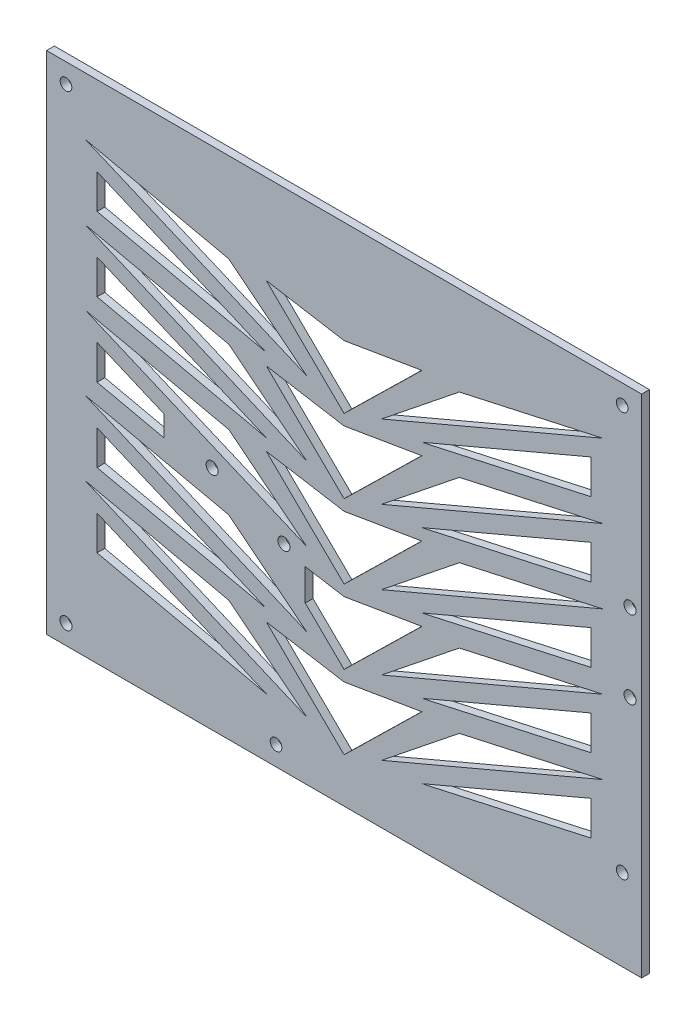
SolidWorks part; units mm, degrees
material "PE 低密度结膜"
ref_plane "前视基准面" through (0, 0, 0) normal (0, 0, 1) x (1, 0, 0)
ref_plane "上视基准面" through (0, 0, 0) normal (0, 1, 0) x (1, 0, 0)
ref_plane "右视基准面" through (0, 0, 0) normal (1, 0, 0) x (0, 0, -1)
sketch "草图1" plane through (0, 0, 0) normal (0, 0, 1) x (1, 0, 0)
  line L1 (-76.5, -55) -> (76.5, -55)
  line L2 (-76.5, -55) -> (-76.5, 55)
  line L3 (-76.5, 55) -> (76.5, 55)
  line L4 (76.5, -55) -> (76.5, 55)
  line L5 (-76.5, -55) -> (76.5, 55) construction
  line L6 (-76.5, 55) -> (76.5, -55) construction
  point P0 (0, 0)
  dimension "D1" = 110
  dimension "D2" = 153
extrude "凸台-拉伸1" add sketch "草图1" along normal blind 2
sketch "草图2" plane through (0, 0, 2) normal (0, 0, 1) x (1, 0, 0)
  circle A0 centre (-33.9424, 3.3504) radius 1.55
  circle A1 centre (-15.4689, -4.3131) radius 1.55
  dimension "D1" = 3.1
  dimension "D2" = 3.1
extrude "切除-拉伸1" cut sketch "草图2" against normal blind 10
sketch "草图3" plane through (0, 0, 2) normal (0, 0, 1) x (1, 0, 0)
  circle A0 centre (73.5, 26) radius 1.55
  circle A1 centre (73.5, 6) radius 1.55
  dimension "D1" = 3.1
extrude "切除-拉伸2" cut sketch "草图3" against normal blind 10
sketch "草图4" plane through (0, 0, 12) normal (0, 0, 1) x (1, 0, 0)
  circle A0 centre (71.5, -34) radius 1.5
extrude "切除-拉伸3" cut sketch "草图4" against normal blind 14
sketch "草图6" plane through (0, 0, 2) normal (0, 0, 1) x (1, 0, 0)
  circle A0 centre (-71.5, -50) radius 1.55
  dimension "D1" = 3.1
extrude "切除-拉伸4" cut sketch "草图6" against normal blind 14
sketch "草图9" plane through (0, 0, 12) normal (0, 0, 1) x (1, 0, 0)
  circle A0 centre (-71.5, 70) radius 1.5
extrude "切除-拉伸6" cut sketch "草图9" against normal blind 14 rebuild error yes
sketch "草图10" plane through (0, 0, 12) normal (0, 0, 1) x (1, 0, 0)
  circle A0 centre (-17.5, -50) radius 1.5
extrude "切除-拉伸7" cut sketch "草图10" against normal blind 21
sketch "Sketch2" plane through (0, 0, 0) normal (0, 0, -1) x (-1, 0, 0)
  line L0 (-76.5, -55) -> (-76.5, 55) construction
  line L1 (-76.5, 55) -> (76.5, 55)
  line L2 (-76.5, 55) -> (-76.5, 75)
  line L3 (-76.5, 75) -> (76.5, 75)
  line L4 (76.5, 55) -> (76.5, 75)
  line L5 (-76.5, 55) -> (76.5, 55) construction
  circle A0 centre (-71.5, 70) radius 1.5
  circle A1 centre (71.5, 70) radius 1.5
  dimension "D1" = 3
  dimension "D2" = 5
  dimension "D3" = 5
  dimension "D4" = 3
  dimension "D5" = 5
  dimension "D7" = 5
  dimension "D6" = 20
extrude "Boss-Extrude1" add sketch "Sketch2" against normal up to surface (2 mm away) up to face at (-19, -50, 2)
sketch "Sketch4" plane through (0, 0, 0) normal (0, 0, -1) x (-1, 0, 0)
  line L0 (0, 75) -> (0, -55) construction
  line L1 (76.5, 75) -> (-76.5, 75) construction
  line L2 (76.5, -55) -> (-76.5, -55) construction
  line L3 (0, 29.6526) -> (20, 33.0228)
  line L7 (9.6268, 17.0228) -> (29.6268, 33.0228)
  line L8 (29.6268, 33.0228) -> (66.5, 41.1778)
  line L9 (66.5, 41.1778) -> (9.6268, 17.0228)
  line L10 (76.5, 75) -> (76.5, -55) construction
  line L11 (20, 17.0228) -> (63.5111, 35.5027)
  line L12 (20, 17.0228) -> (63.5111, 26.6459)
  line L13 (63.5111, 26.6459) -> (63.5111, 35.5027)
  line L14 (-63.5111, 26.6459) -> (-63.5111, 35.5027)
  line L15 (-20, 17.0228) -> (-63.5111, 26.6459)
  line L16 (-20, 17.0228) -> (-63.5111, 35.5027)
  line L17 (-66.5, 41.1778) -> (-9.6268, 17.0228)
  line L18 (-29.6268, 33.0228) -> (-66.5, 41.1778)
  line L19 (-9.6268, 17.0228) -> (-29.6268, 33.0228)
  line L21 (0, 29.6526) -> (-20, 33.0228)
  line L22 (-20, 33.0228) -> (0, 13.4456)
  line L23 (0, 13.4456) -> (20, 33.0228)
  dimension "D1" = 20
  dimension "D5" = 10
extrude "Cut-Extrude2" cut sketch "Sketch4" against normal blind 10
pattern_linear "LPattern2" count 2 spacing 19 along (0, 1, 0) of "Cut-Extrude2"
pattern_linear "LPattern3" count 4 spacing 19 along (0, -1, 0) of "Cut-Extrude2"
sketch "Sketch5" plane through (0, 0, 0) normal (0, 0, -1) x (-1, 0, 0)
  line L0 (46.3639, 9.22) -> (46.3639, 3.8535)
  line L1 (63.5111, 16.5027) -> (35.0636, 4.4206) construction
  line L2 (20, -1.9772) -> (63.5111, 7.6459) construction
  line L3 (46.3639, 3.8535) -> (20, -1.9772)
  line L4 (20, -1.9772) -> (46.3639, 9.22)
  line L5 (10.0328, -6.6568) -> (10, -14.7658)
  line L6 (15.0634, -5.8091) -> (0, -8.3474) construction
  line L7 (0, -24.5544) -> (20, -4.9772) construction
  line L8 (10, -14.7658) -> (20, -4.9772)
  line L9 (20, -4.9772) -> (10.0328, -6.6568)
  circle A0 centre (33.9424, 3.3504) radius 1.55
  circle A1 centre (15.4689, -4.3131) radius 1.55
extrude "Boss-Extrude2" add sketch "Sketch5" against normal up to surface (2 mm away) contours A1 L9 L5 L8 | A0 L4 L3 L0 region at (-37.866, 3.7564, 0) region at (-13.337, -8.8093, 0) up to face at (-35.2512, -7.5922, 2)
